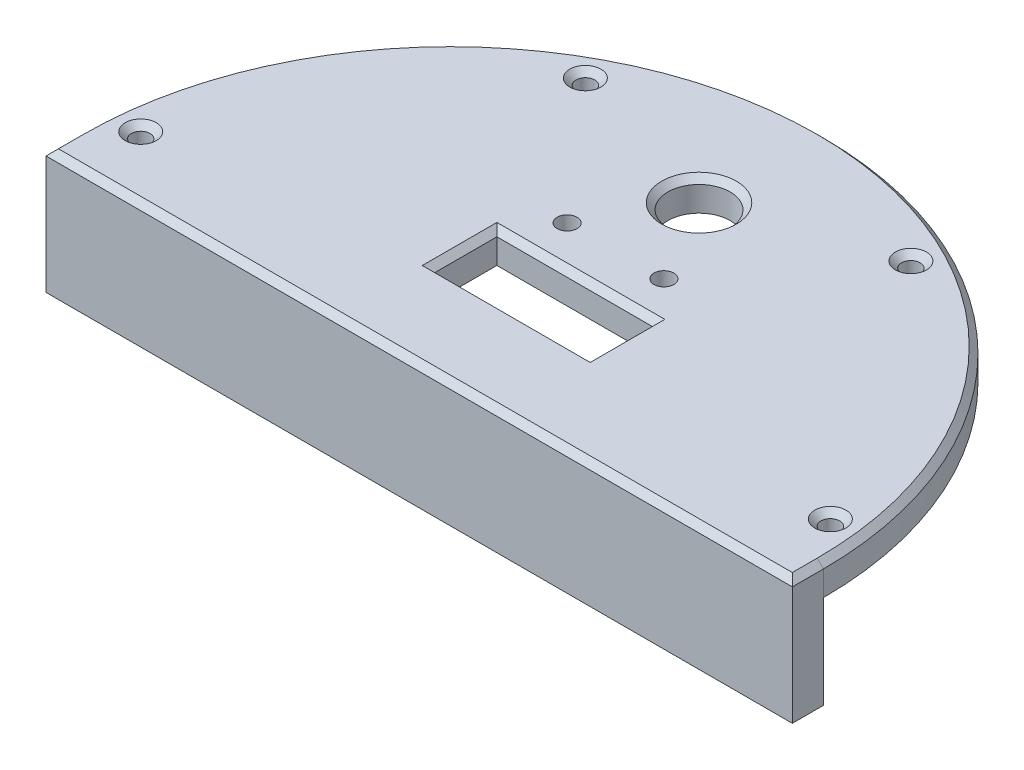
SolidWorks part; units mm, degrees
ref_plane "Front Plane" through (0, 0, 0) normal (0, 0, 1) x (1, 0, 0)
ref_plane "Top Plane" through (0, 0, 0) normal (0, 1, 0) x (1, 0, 0)
ref_plane "Right Plane" through (0, 0, 0) normal (1, 0, 0) x (0, 0, -1)
sketch "Sketch1" plane through (0, 0, 0) normal (0, 1, 0) x (1, 0, 0)
  line L0 (-60, 0) -> (-25.75, 0)
  line L1 (25.75, 0) -> (60, 0)
  line L2 (-25.75, 0) -> (25.75, 0)
  arc A0 (60, 0) -> (-60, 0) centre (0, 0) ccw
  dimension "D2" = 120
extrude "Boss-Extrude1" add sketch "Sketch1" along normal blind 5
sketch "Sketch2" plane through (0, 5, 0) normal (0, 1, 0) x (1, 0, 0)
  circle A0 centre (-54.7723, 5) radius 1.5
  arc A1 (60, 0) -> (-60, 0) centre (0, 0) ccw construction
  dimension "D1" = 3
  dimension "D2" = 5
  dimension "D3" = 55
extrude "Cut-Extrude1" cut sketch "Sketch2" against normal blind 5
pattern_circular "CirPattern1" count 4 every 56 about axis through (0, 5, 0) along (0, 1, 0) of "Cut-Extrude1" reverse direction yes
sketch "Sketch4" plane through (0, 0, 0) normal (0, -1, 0) x (-1, 0, 0)
  line L1 (10.555, 13.4821) -> (-10.555, 13.4821)
  line L2 (10.555, 13.4821) -> (10.555, 29.2121)
  line L3 (10.555, 29.2121) -> (-10.555, 29.2121)
  line L4 (-10.555, 13.4821) -> (-10.555, 29.2121)
  circle A0 centre (7.785, 26.5721) radius 1.5
  circle A1 centre (-7.775, 26.5721) radius 1.5
  dimension "D4" = 3
  dimension "D5" = 2.77
  dimension "D6" = 2.64
  dimension "D7" = 3
  dimension "D8" = 15.56
  dimension "D9" = 2.64
  dimension "D1" = 21.11
  dimension "D2" = 10.555
  dimension "D3" = 15.73
sketch "Sketch5" plane through (0, 0, 0) normal (0, -1, 0) x (1, 0, 0)
  circle A1 centre (7.775, -26.5721) radius 1.6
  circle A2 centre (7.775, -26.5721) radius 1.6
  circle A3 centre (-7.785, -26.5721) radius 1.6
  dimension "D1" = 3.2
  dimension "D2" = 3.2
sketch "Sketch7" plane through (0, 0, 0) normal (0, -1, 0) x (1, 0, 0)
  line L1 (-10.555, -13.4821) -> (10.555, -13.4821)
  line L2 (-10.555, -13.4821) -> (-10.555, -29.2121)
  line L3 (-10.555, -29.2121) -> (10.555, -29.2121)
  line L4 (10.555, -13.4821) -> (10.555, -29.2121)
sketch "Sketch8" plane through (0, 0, 0) normal (0, -1, 0) x (-1, 0, 0)
  line L0 (60, 0) -> (-60, 0) construction
  line L1 (12.5, 10) -> (-12.5, 10)
  line L2 (12.5, 10) -> (12.5, 20)
  line L3 (12.5, 20) -> (-12.5, 20)
  line L4 (-12.5, 10) -> (-12.5, 20)
  dimension "D1" = 25
  dimension "D2" = 12.5
  dimension "D3" = 10
  dimension "D4" = 10
extrude "Cut-Extrude3" cut sketch "Sketch8" against normal mid plane 10
sketch "Sketch9" plane through (0, 0, 0) normal (0, 0, 1) x (1, 0, 0)
  line L1 (-60, 5) -> (60, 5)
  line L2 (-60, 5) -> (-60, -15)
  line L3 (-60, -15) -> (60, -15)
  line L4 (60, 5) -> (60, -15)
  dimension "D1" = 120
  dimension "D2" = 20
extrude "Boss-Extrude5" add sketch "Sketch9" along normal blind 5
sketch "Sketch10" plane through (0, 5, 0) normal (0, 1, 0) x (1, 0, 0)
  line L0 (0, -5) -> (0, 60) construction
  line L1 (60, -5) -> (-60, -5) construction
  circle A0 centre (0, 40) radius 5
  arc A1 (60, 0) -> (-60, 0) centre (0, 0) ccw construction
  point P9 (0, 0)
  dimension "D1" = 10
  dimension "D3" = 40
extrude "Cut-Extrude4" cut sketch "Sketch10" against normal blind 10
chamfer "Chamfer1" distance 1 angle 45 9 edges at (54.303, 5, -7.9643) (12.5, 5, -15) (0, 5, -10) (-12.5, 5, -15) (0, 5, -20) (23.7632, 5, -49.4728) (-27.7266, 5, -47.3654) (0, 5, -35) (-54.7723, 5, -3.5)
chamfer "Chamfer2" distance 1 angle 45 4 edges at (60, 5, 2.5) (-60, 5, 2.5) (0, 5, -60) (0, 5, 5)
extrude "Cut-Extrude5" cut sketch "Sketch5" against normal blind 10 contours A3 | A1 region at (7.775, 0, -26.5721) region at (-7.785, 0, -26.5721)
sketch "Sketch11" plane through (0, 0, 0) normal (0, -1, 0) x (1, 0, 0)
  circle A0 centre (-7.785, -26.5721) radius 1.6
  circle A1 centre (-7.785, -26.5721) radius 2.5
  circle A2 centre (7.775, -26.5721) radius 1.6
  circle A3 centre (7.775, -26.5721) radius 2.5
  dimension "D1" = 5
  dimension "D2" = 5
extrude "Boss-Extrude6" add sketch "Sketch11" along normal blind 1
fillet "Fillet5" radius 1 2 edges at (7.775, 0, -24.0721) (-7.785, 0, -24.0721)
